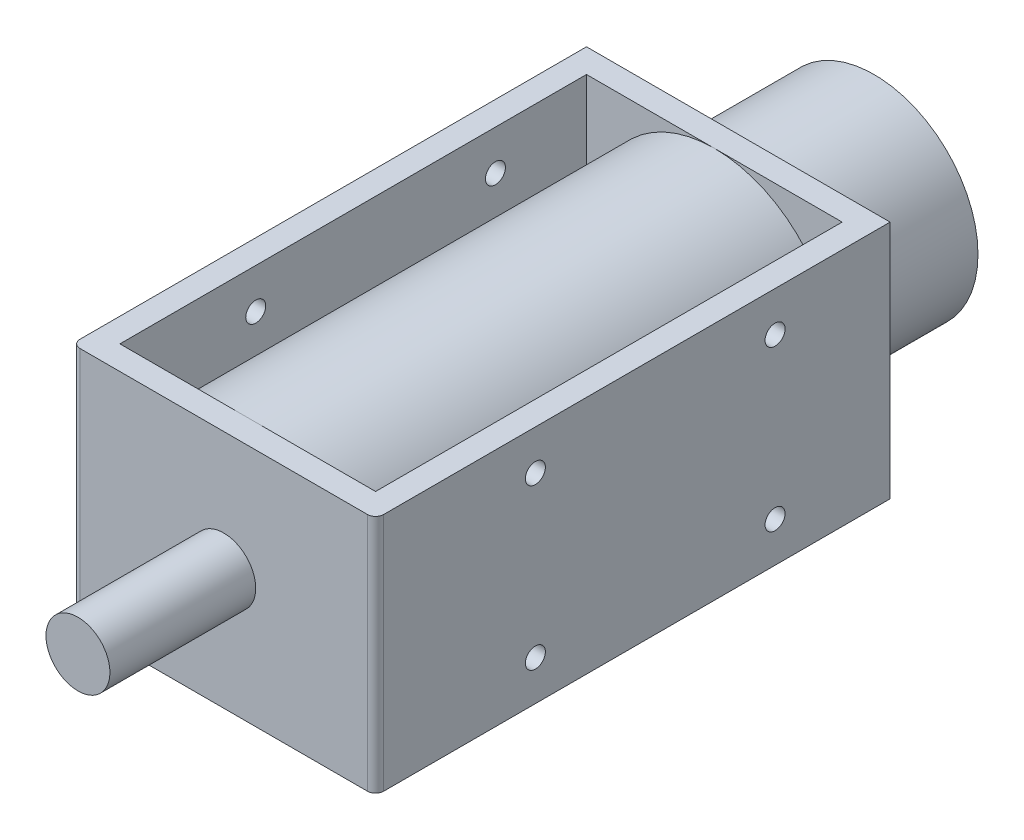
SolidWorks part; units mm, degrees
material "Plain Carbon Steel"
ref_plane "Front Plane" through (0, 0, 0) normal (0, 0, 1) x (1, 0, 0)
ref_plane "Top Plane" through (0, 0, 0) normal (0, 1, 0) x (1, 0, 0)
ref_plane "Right Plane" through (0, 0, 0) normal (1, 0, 0) x (0, 0, -1)
sketch "Sketch1" plane through (0, 0, 0) normal (0, 0, 1) x (1, 0, 0)
  line L1 (-19, -15) -> (19, -15)
  line L2 (-19, -15) -> (-19, 15)
  line L3 (-19, 15) -> (19, 15)
  line L4 (19, -15) -> (19, 15)
  line L5 (-19, -15) -> (19, 15) construction
  line L6 (-19, 15) -> (19, -15) construction
  point P0 (0, 0)
  dimension "D1" = 30
  dimension "D2" = 38
extrude "Boss-Extrude1" add sketch "Sketch1" along normal blind 64.4
sketch "Sketch2" plane through (0, 0, 64.4) normal (0, 0, 1) x (1, 0, 0)
  circle A0 centre (0, 0) radius 4
  dimension "D1" = 8
sketch "Sketch3" plane through (0, 0, 0) normal (0, 0, -1) x (-1, 0, 0)
  circle A0 centre (0, 0) radius 13
  dimension "D1" = 26
extrude "Boss-Extrude3" add sketch "Sketch3" along normal blind 17
extrude "Boss-Extrude4" add sketch "Sketch2" along normal blind 18.25
sketch "Sketch16" plane through (0, -15, 0) normal (0, -1, 0) x (1, 0, 0)
  line L16 (16, 61.4) -> (-16, 61.4)
  line L17 (16, 3) -> (16, 61.4)
  line L18 (-16, 3) -> (16, 3)
  line L19 (-16, 61.4) -> (-16, 3)
  line L20 (16, 61.4) -> (-16, 61.4)
  line L21 (16, 3) -> (16, 61.4)
  line L22 (-16, 3) -> (16, 3)
  line L23 (-16, 61.4) -> (-16, 3)
  dimension "D1" = 3
extrude "Cut-Extrude1" cut sketch "Sketch16" against normal through all
sketch "Sketch17" plane through (0, 0, 61.4) normal (0, 0, -1) x (-1, 0, 0)
  line L0 (-16, -15) -> (16, -15) construction
  circle A0 centre (0, 0) radius 15
extrude "Boss-Extrude9" add sketch "Sketch17" along normal up to surface (58.4 mm away) up to face at (0, 0, 3)
fillet "Fillet1" radius 1 2 edges at (19, 0, 64.4) (-19, 0, 64.4)
hole_wizard "M3x0.5 Tapped Hole1" positions "Sketch18" profile "Sketch19" tap size "M3x0.5" standard "ANSI Metric" end condition up to next
sketch "Sketch18" plane through (-19, 0, 0) normal (-1, 0, 0) x (0, 0, 1)
  line L0 (64.4, 15) -> (64.4, -15) construction
  line L1 (0, 0) -> (63.4, 0) construction
  line L2 (0, 15) -> (0, -15) construction
  line L3 (63.4, -15) -> (63.4, 15) construction
  point P0 (14.4, -10)
  point P6 (44.4, -10)
  point P21 (44.4, 10)
  point P22 (14.4, 10)
  dimension "D1" = 20
  dimension "D2" = 30
  dimension "D3" = 10
  dimension "D4" = 10
sketch "Sketch19" plane through (-19, -10, 14.4) normal (0, 1, 0) x (0, 0, 1)
  line L0 (0, 0) -> (0, 3)
  line L1 (0, 3) -> (1.25, 3)
  line L2 (1.25, 3) -> (1.25, 0)
  line L5 (1.25, 0) -> (0, 0)
  line L11 (0, -6.35) -> (0, 107.95) construction
  dimension "Thru Tap Drill Dia." = 2.5
  dimension "Thru Tap Drill Depth" = 3
cosmetic thread "Hole Thread1" parameters "D2"=3
cosmetic thread "Hole Thread2" parameters "D2"=3
cosmetic thread "Hole Thread3" parameters "D2"=3
cosmetic thread "Hole Thread4" parameters "D2"=3
hole_wizard "M3x0.5 Tapped Hole2" positions "Sketch20" profile "Sketch21" tap size "M3x0.5" standard "ANSI Metric" end condition up to next
sketch "Sketch20" plane through (19, 0, 0) normal (1, 0, 0) x (0, 0, -1)
  point P0 (-14.4, 10)
  point P3 (-14.4, -10)
  point P6 (-44.4, -10)
  point P9 (-44.4, 10)
sketch "Sketch21" plane through (19, 10, 14.4) normal (0, 1, 0) x (0, 0, -1)
  line L0 (0, 0) -> (0, 3)
  line L1 (0, 3) -> (1.25, 3)
  line L2 (1.25, 3) -> (1.25, 0)
  line L5 (1.25, 0) -> (0, 0)
  line L11 (0, -6.35) -> (0, 107.95) construction
  dimension "Thru Tap Drill Dia." = 2.5
  dimension "Thru Tap Drill Depth" = 3
cosmetic thread "Hole Thread5" parameters "D2"=3
cosmetic thread "Hole Thread6" parameters "D2"=3
cosmetic thread "Hole Thread7" parameters "D2"=3
cosmetic thread "Hole Thread8" parameters "D2"=3
